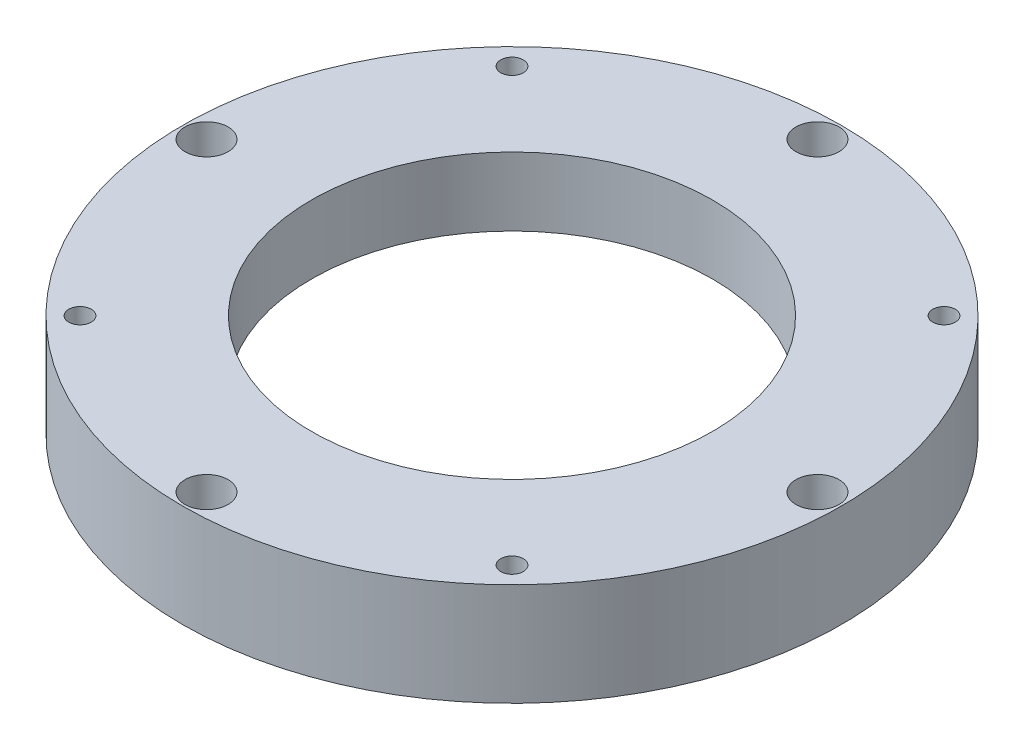
SolidWorks part; units mm, degrees
ref_plane "Front Plane" through (0, 0, 0) normal (0, 0, 1) x (1, 0, 0)
ref_plane "Top Plane" through (0, 0, 0) normal (0, 1, 0) x (1, 0, 0)
ref_plane "Right Plane" through (0, 0, 0) normal (1, 0, 0) x (0, 0, -1)
sketch "Sketch1" plane through (0, 0, 0) normal (0, 1, 0) x (1, 0, 0)
  line L0 (0, 0) -> (42.5, 0) construction
  circle A0 centre (0, 0) radius 45.85
  circle A1 centre (0, 0) radius 27.9
  circle A2 centre (42.5, 0) radius 1.5635
  circle A3 centre (30.052, -30.052) radius 1.5635
  circle A4 centre (0, -42.5) radius 1.5635
  circle A5 centre (0, 0) radius 40
  circle A6 centre (-30.052, -30.052) radius 1.5635
  circle A7 centre (-42.5, 0) radius 1.5635
  circle A8 centre (-30.052, 30.052) radius 1.5635
  circle A9 centre (0, 42.5) radius 1.5635
  circle A10 centre (30.052, 30.052) radius 1.5635
  point P13 (0, 0)
  dimension "D1" = 91.7
  dimension "D2" = 55.8
  dimension "D4" = 3.127
  dimension "D6" = 80
  dimension "D3" = 42.5
  dimension "D5" = 8
extrude "Boss-Extrude1" add sketch "Sketch1" against normal blind 4.7625 contours A0 A5 A2 A4 A3 region at (-44.5532, 0, 0)
extrude "Boss-Extrude2" add sketch "Sketch1<4>" along normal blind 4.7625 contours A1 A5 | A0 A5 A2 A4 A3 region at (-44.5532, 0, 0) region at (-38.8686, 0, 0)
sketch "Sketch1<4>" plane through (0, 0, 0) normal (0, 1, 0) x (1, 0, 0) same geometry as "Sketch1"
sketch "Sketch4" plane through (0, 4.7625, 0) normal (0, 1, 0) x (1, 0, 0)
  line L0 (28.4932, -27.352) -> (26.9343, -30.052)
  line L7 (30.052, 33.1697) -> (27.352, 31.6109)
  line L8 (27.352, 31.6109) -> (27.352, 28.4932)
  line L9 (27.352, 28.4932) -> (30.052, 26.9343)
  line L10 (30.052, 26.9343) -> (32.752, 28.4932)
  line L11 (32.752, 28.4932) -> (32.752, 31.6109)
  line L12 (32.752, 31.6109) -> (30.052, 33.1697)
  line L13 (31.6109, -27.352) -> (28.4932, -27.352)
  line L14 (33.1697, -30.052) -> (31.6109, -27.352)
  line L15 (31.6109, -32.752) -> (33.1697, -30.052)
  line L16 (28.4932, -32.752) -> (31.6109, -32.752)
  line L17 (26.9343, -30.052) -> (28.4932, -32.752)
  line L18 (-27.352, -28.4932) -> (-30.052, -26.9343)
  line L19 (-27.352, -31.6109) -> (-27.352, -28.4932)
  line L20 (-30.052, -33.1697) -> (-27.352, -31.6109)
  line L21 (-32.752, -31.6109) -> (-30.052, -33.1697)
  line L22 (-32.752, -28.4932) -> (-32.752, -31.6109)
  line L23 (-30.052, -26.9343) -> (-32.752, -28.4932)
  line L24 (-28.4932, 27.352) -> (-26.9343, 30.052)
  line L25 (-31.6109, 27.352) -> (-28.4932, 27.352)
  line L26 (-33.1697, 30.052) -> (-31.6109, 27.352)
  line L27 (-31.6109, 32.752) -> (-33.1697, 30.052)
  line L28 (-28.4932, 32.752) -> (-31.6109, 32.752)
  line L29 (-26.9343, 30.052) -> (-28.4932, 32.752)
  circle A0 centre (30.052, 30.052) radius 2.7 construction
  point P1 (31.402, 32.3903)
  point P32 (0, 0)
  dimension "D1" = 5.4
  dimension "D2" = 4
extrude "Cut-Extrude2" cut sketch "Sketch4" against normal blind 4.7625
sketch "Sketch3" plane through (0, 4.7625, 0) normal (0, 1, 0) x (1, 0, 0)
  circle A6 centre (0, -42.5) radius 1.5635 construction
  circle A7 centre (42.5, 0) radius 1.5635 construction
  circle A8 centre (0, 42.5) radius 1.5635 construction
  circle A9 centre (-42.5, 0) radius 1.5635 construction
  circle A10 centre (0, 0) radius 27.9 construction
  circle A11 centre (0, 0) radius 45.85 construction
  circle A12 centre (0, -42.5) radius 1.5635
  circle A13 centre (42.5, 0) radius 1.5635
  circle A14 centre (0, 42.5) radius 1.5635
  circle A15 centre (-42.5, 0) radius 1.5635
  circle A16 centre (0, 0) radius 27.9
  circle A17 centre (0, 0) radius 45.85
  circle A18 centre (0, 42.5) radius 3
  circle A19 centre (42.5, 0) radius 3
  circle A20 centre (0, -42.5) radius 3
  circle A21 centre (-42.5, 0) radius 3
  circle A22 centre (-30.052, 30.052) radius 1.565
  circle A23 centre (30.052, 30.052) radius 1.565
  circle A24 centre (30.052, -30.052) radius 1.565
  circle A25 centre (-30.052, -30.052) radius 1.565
  circle M1 centre (0, 0) radius 27.9
  circle M6 centre (0, 0) radius 45.85
  line M21 (-33.1697, 30.052) -> (-31.6109, 32.752)
  line M22 (-31.6109, 32.752) -> (-28.4932, 32.752)
  line M23 (-28.4932, 32.752) -> (-26.9343, 30.052)
  line M24 (-26.9343, 30.052) -> (-28.4932, 27.352)
  line M25 (-28.4932, 27.352) -> (-31.6109, 27.352)
  line M26 (-31.6109, 27.352) -> (-33.1697, 30.052)
  line M27 (-30.052, -33.1697) -> (-32.752, -31.6109)
  line M28 (-32.752, -31.6109) -> (-32.752, -28.4932)
  line M29 (-32.752, -28.4932) -> (-30.052, -26.9343)
  line M30 (-30.052, -26.9343) -> (-27.352, -28.4932)
  line M31 (-27.352, -28.4932) -> (-27.352, -31.6109)
  line M32 (-27.352, -31.6109) -> (-30.052, -33.1697)
  line M33 (33.1697, -30.052) -> (31.6109, -32.752)
  line M34 (31.6109, -32.752) -> (28.4932, -32.752)
  line M35 (28.4932, -32.752) -> (26.9343, -30.052)
  line M36 (26.9343, -30.052) -> (28.4932, -27.352)
  line M37 (28.4932, -27.352) -> (31.6109, -27.352)
  line M38 (31.6109, -27.352) -> (33.1697, -30.052)
  line M39 (30.052, 33.1697) -> (32.752, 31.6109)
  line M40 (32.752, 31.6109) -> (32.752, 28.4932)
  line M41 (32.752, 28.4932) -> (30.052, 26.9343)
  line M42 (30.052, 26.9343) -> (27.352, 28.4932)
  line M43 (27.352, 28.4932) -> (27.352, 31.6109)
  line M44 (27.352, 31.6109) -> (30.052, 33.1697)
  dimension "D1" = 6
  dimension "D2" = 3.13
extrude "Boss-Extrude3" add sketch "Sketch3" along normal blind 4.7625 contours A21 A20 A19 A18 M6 M1 M44 M39 M40 M41 M42 M43 M38 M33 M34 M35 M36 M37 M32 M27 M28 M29 M30 M31 M26 M21 M22 M23 M24 M25 | A22 M21 M26 M25 M24 M23 M22 | A23 M39 M44 M43 M42 M41 M40 | A24 M33 M38 M37 M36 M35 M34 | A25 M27 M32 M31 M30 M29 M28 region at (-45.7203, 4.7625, 0) region at (-32.3189, 4.7625, -31.3608) region at (-31.3608, 4.7625, 32.3189) region at (32.3189, 4.7625, 31.3608) region at (31.3608, 4.7625, -32.3189)
sketch "Sketch5" plane through (0, 9.525, 0) normal (0, 1, 0) x (1, 0, 0)
  line L0 (0, 0) -> (30.052, 30.052) construction
  circle A0 centre (0, 42.5) radius 3 construction
  circle A1 centre (30.052, 30.052) radius 1.565 construction
  circle A2 centre (42.5, 0) radius 3 construction
  circle A3 centre (30.052, -30.052) radius 1.565 construction
  circle A4 centre (0, -42.5) radius 3 construction
  circle A5 centre (-30.052, -30.052) radius 1.565 construction
  circle A6 centre (-42.5, 0) radius 3 construction
  circle A7 centre (-30.052, 30.052) radius 1.565 construction
  circle A8 centre (0, 0) radius 45.85 construction
  circle A9 centre (0, 0) radius 27.9 construction
  circle A10 centre (0, 42.5) radius 3
  circle A11 centre (30.052, 30.052) radius 1.565
  circle A12 centre (42.5, 0) radius 3
  circle A13 centre (30.052, -30.052) radius 1.565
  circle A14 centre (0, -42.5) radius 3
  circle A15 centre (-30.052, -30.052) radius 1.565
  circle A16 centre (-42.5, 0) radius 3
  circle A17 centre (-30.052, 30.052) radius 1.565
  circle A18 centre (0, 0) radius 45.85
  circle A19 centre (0, 0) radius 27.9
  arc A20 (6.31, 31.2697) -> (18.4511, 26.0224) centre (0, 0) cw
  arc A21 (4.6718, 37.2871) -> (6.4423, 39.762) centre (0, 42.5) ccw
  arc A22 (24.5734, 31.0284) -> (24.5119, 29.527) centre (30.052, 30.052) ccw
  arc A23 (24.5119, 29.527) -> (18.4511, 26.0224) centre (20.6784, 29.1636) cw
  arc A24 (4.6718, 37.2871) -> (6.31, 31.2697) centre (7, 34.6892) ccw
  arc A25 (22.8162, 35.0834) -> (24.5734, 31.0284) centre (20.6354, 31.7302) cw
  arc A26 (8.6987, 40.936) -> (6.4423, 39.762) centre (8.283, 38.9797) ccw
  arc A27 (22.8162, 35.0834) -> (8.6987, 40.936) centre (0, 0) ccw
  arc A28 (35.0834, 22.8162) -> (31.0284, 24.5734) centre (31.7302, 20.6354) ccw
  arc A29 (31.0284, 24.5734) -> (29.527, 24.5119) centre (30.052, 30.052) cw
  arc A30 (29.527, 24.5119) -> (26.0224, 18.4511) centre (29.1636, 20.6784) ccw
  arc A31 (31.2697, 6.31) -> (26.0224, 18.4511) centre (0, 0) ccw
  arc A32 (35.0834, 22.8162) -> (40.936, 8.6987) centre (0, 0) cw
  arc A33 (40.936, 8.6987) -> (39.762, 6.4423) centre (38.9797, 8.283) cw
  arc A34 (37.2871, 4.6718) -> (39.762, 6.4423) centre (42.5, 0) cw
  arc A35 (37.2871, 4.6718) -> (31.2697, 6.31) centre (34.6892, 7) cw
  arc A36 (37.2871, -4.6718) -> (31.2697, -6.31) centre (34.6892, -7) ccw
  arc A37 (31.2697, -6.31) -> (26.0224, -18.4511) centre (0, 0) cw
  arc A38 (29.527, -24.5119) -> (26.0224, -18.4511) centre (29.1636, -20.6784) cw
  arc A39 (31.0284, -24.5734) -> (29.527, -24.5119) centre (30.052, -30.052) ccw
  arc A40 (35.0834, -22.8162) -> (31.0284, -24.5734) centre (31.7302, -20.6354) cw
  arc A41 (35.0834, -22.8162) -> (40.936, -8.6987) centre (0, 0) ccw
  arc A42 (40.936, -8.6987) -> (39.762, -6.4423) centre (38.9797, -8.283) ccw
  arc A43 (37.2871, -4.6718) -> (39.762, -6.4423) centre (42.5, 0) ccw
  arc A44 (24.5119, -29.527) -> (18.4511, -26.0224) centre (20.6784, -29.1636) ccw
  arc A45 (24.5734, -31.0284) -> (24.5119, -29.527) centre (30.052, -30.052) cw
  arc A46 (22.8162, -35.0834) -> (24.5734, -31.0284) centre (20.6354, -31.7302) ccw
  arc A47 (22.8162, -35.0834) -> (8.6987, -40.936) centre (0, 0) cw
  arc A48 (6.31, -31.2697) -> (18.4511, -26.0224) centre (0, 0) ccw
  arc A49 (4.6718, -37.2871) -> (6.31, -31.2697) centre (7, -34.6892) cw
  arc A50 (4.6718, -37.2871) -> (6.4423, -39.762) centre (0, -42.5) cw
  arc A51 (8.6987, -40.936) -> (6.4423, -39.762) centre (8.283, -38.9797) cw
  arc A52 (-4.6718, -37.2871) -> (-6.31, -31.2697) centre (-7, -34.6892) ccw
  arc A53 (-6.31, -31.2697) -> (-18.4511, -26.0224) centre (0, 0) cw
  arc A54 (-24.5119, -29.527) -> (-18.4511, -26.0224) centre (-20.6784, -29.1636) cw
  arc A55 (-24.5734, -31.0284) -> (-24.5119, -29.527) centre (-30.052, -30.052) ccw
  arc A56 (-22.8162, -35.0834) -> (-24.5734, -31.0284) centre (-20.6354, -31.7302) cw
  arc A57 (-22.8162, -35.0834) -> (-8.6987, -40.936) centre (0, 0) ccw
  arc A58 (-8.6987, -40.936) -> (-6.4423, -39.762) centre (-8.283, -38.9797) ccw
  arc A59 (-4.6718, -37.2871) -> (-6.4423, -39.762) centre (0, -42.5) ccw
  arc A60 (-29.527, -24.5119) -> (-26.0224, -18.4511) centre (-29.1636, -20.6784) ccw
  arc A61 (-31.0284, -24.5734) -> (-29.527, -24.5119) centre (-30.052, -30.052) cw
  arc A62 (-35.0834, -22.8162) -> (-31.0284, -24.5734) centre (-31.7302, -20.6354) ccw
  arc A63 (-35.0834, -22.8162) -> (-40.936, -8.6987) centre (0, 0) cw
  arc A64 (-31.2697, -6.31) -> (-26.0224, -18.4511) centre (0, 0) ccw
  arc A65 (-37.2871, -4.6718) -> (-31.2697, -6.31) centre (-34.6892, -7) cw
  arc A66 (-37.2871, -4.6718) -> (-39.762, -6.4423) centre (-42.5, 0) cw
  arc A67 (-40.936, -8.6987) -> (-39.762, -6.4423) centre (-38.9797, -8.283) cw
  arc A68 (-37.2871, 4.6718) -> (-31.2697, 6.31) centre (-34.6892, 7) ccw
  arc A69 (-31.2697, 6.31) -> (-26.0224, 18.4511) centre (0, 0) cw
  arc A70 (-29.527, 24.5119) -> (-26.0224, 18.4511) centre (-29.1636, 20.6784) cw
  arc A71 (-31.0284, 24.5734) -> (-29.527, 24.5119) centre (-30.052, 30.052) ccw
  arc A72 (-35.0834, 22.8162) -> (-31.0284, 24.5734) centre (-31.7302, 20.6354) cw
  arc A73 (-35.0834, 22.8162) -> (-40.936, 8.6987) centre (0, 0) ccw
  arc A74 (-40.936, 8.6987) -> (-39.762, 6.4423) centre (-38.9797, 8.283) ccw
  arc A75 (-37.2871, 4.6718) -> (-39.762, 6.4423) centre (-42.5, 0) ccw
  arc A76 (-24.5119, 29.527) -> (-18.4511, 26.0224) centre (-20.6784, 29.1636) ccw
  arc A77 (-24.5734, 31.0284) -> (-24.5119, 29.527) centre (-30.052, 30.052) cw
  arc A78 (-22.8162, 35.0834) -> (-24.5734, 31.0284) centre (-20.6354, 31.7302) ccw
  arc A79 (-22.8162, 35.0834) -> (-8.6987, 40.936) centre (0, 0) cw
  arc A80 (-6.31, 31.2697) -> (-18.4511, 26.0224) centre (0, 0) ccw
  arc A81 (-4.6718, 37.2871) -> (-6.31, 31.2697) centre (-7, 34.6892) cw
  arc A82 (-4.6718, 37.2871) -> (-6.4423, 39.762) centre (0, 42.5) cw
  arc A83 (-8.6987, 40.936) -> (-6.4423, 39.762) centre (-8.283, 38.9797) cw
  point P137 (0, 0)
  dimension "D1" = 4
  dimension "D2" = 4
  dimension "D3" = 4
  dimension "D4" = 4
  dimension "D5" = 12
  dimension "D8" = 2
  dimension "D9" = 4
  dimension "D7" = 14
  dimension "D6" = 4
extrude "Cut-Extrude3" [suppressed] cut sketch "Sketch5" against normal blind 4.7625 contours A75 A68 A69 A70 A71 A72 A73 A74 | A83 A79 A78 A77 A76 A80 A81 A82 | A25 A27 A26 A21 A24 A20 A23 A22 | A35 A34 A33 A32 A28 A29 A30 A31 | A43 A36 A37 A38 A39 A40 A41 A42 | A51 A47 A46 A45 A44 A48 A49 A50 | A59 A52 A53 A54 A55 A56 A57 A58 | A67 A63 A62 A61 A60 A64 A65 A66
equation "\"bearing_21_OD\"= 21mm"
equation "\"pin_cirlce_diameter\"= 75mm"
equation "\"pin_diam\"= 6mm"
equation "\"gear_thickness\"= 4mm"
equation "\"ball_bearing_diam\"= 3.214mm"
equation "\"bearing_21_outer_clearance\"= 0.127mm'change this"
equation "\"bearing_15_OD\"= 15mm"
equation "\"bearing_15_outer_clearance\"= 0mm'change this"
equation "\"thrust_bearing_thickness\"= 5mm'measure this irl and change"
equation "\"D1@Boss-Extrude1\"=\"sheetThickness\""
equation "\"largeBearOD\"= 21mm"
equation "\"largeBearID\"= 15mm"
equation "\"largeBearOTight\"= 0.28mm'calibrate - hold onto gears"
equation "\"largeBearITight\"= 0mm'calibrate - hold onto eccentric nut"
equation "\"largeBearFlangeDiam\"= 22.5mm"
equation "\"largeBearFlangeWidth\"= 0.8mm"
equation "\"smallBearOD\"= 15mm"
equation "\"smallBearOTight\"= 0.2mm'calibrate - hold onto bottom of gearbox"
equation "\"smallBearOLoose\"= 0mm'calibrate - able to take off topHat"
equation "\"smallBearID\"= 10mm"
equation "\"smallBearITight\"= 0mm'hold onto "
equation "\"pinCircleDiam\"= 75mm"
equation "\"pinDiam\"= 6mm"
equation "\"sheetThickness\"= 0.1875in"
equation "\"ballBearDiam\"= 3.5mm"
equation "\"thrustBearingThickness\"= 5mm'measure this irl and change"
equation "\"thrustBearingID\"= 0mm'measure this irl and change"
equation "\"thrustBearingOD\"= 0mm'measure this irl and change"
equation "\"eccentricity\"= 1mm"
equation "\"D1@Boss-Extrude2\"=\"sheetThickness\""
equation "\"D1@Boss-Extrude3\"=\"sheetThickness\""
equation "\"D1@Cut-Extrude2\"=\"sheetThickness\""
equation "\"D1@Cut-Extrude3\"=\"sheetThickness\""
